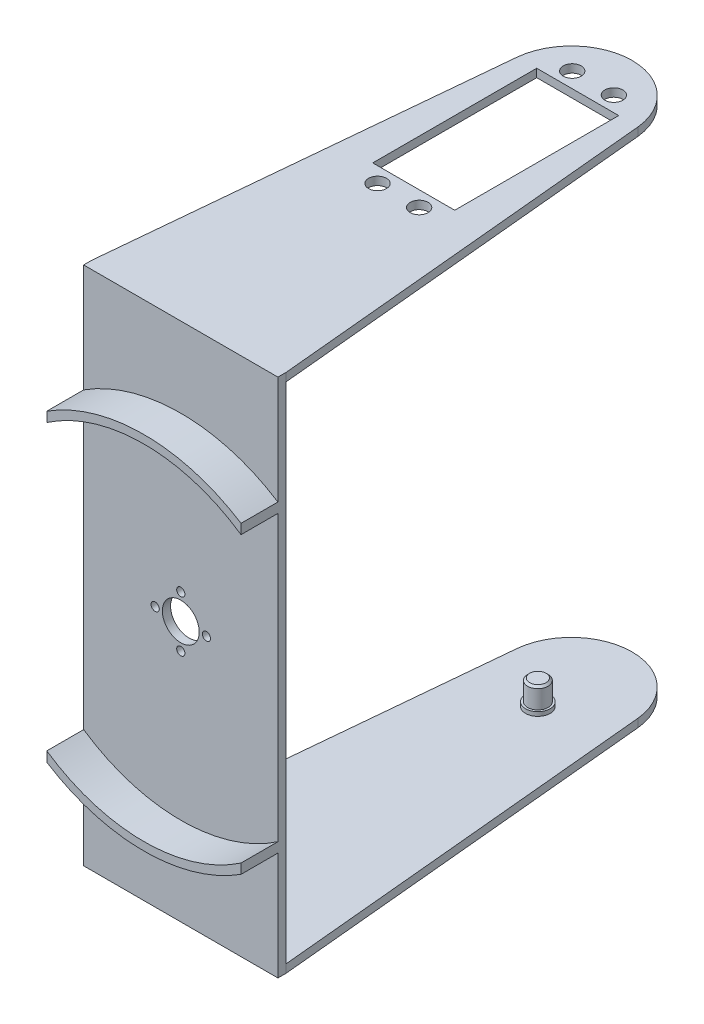
SolidWorks part; units mm, degrees
ref_plane "Front Plane" through (0, 0, 0) normal (0, 0, 1) x (1, 0, 0)
ref_plane "Top Plane" through (0, 0, 0) normal (0, 1, 0) x (1, 0, 0)
ref_plane "Right Plane" through (0, 0, 0) normal (1, 0, 0) x (0, 0, -1)
sketch "Sketch1" plane through (0, 0, 0) normal (0, 1, 0) x (1, 0, 0)
  line L0 (0, 0) -> (10, 0)
  line L1 (10, 0) -> (10, -40)
  line L2 (0, 0) -> (-10, 0)
  line L3 (-10, 0) -> (-10, -40)
  line L4 (-10, -40) -> (10, -40)
  line L5 (0, -46.4243) -> (0, 6.4077) construction
  line L6 (-14.7387, 0) -> (-23.7006, -94.809)
  line L7 (-9.906, -20.0083) -> (9.906, -20.0083) construction
  line L8 (0, -46.4243) -> (0, -94.809) construction
  line L9 (-23.7006, -94.809) -> (0, -94.809) construction
  line L21 (0, 6.4077) -> (0, 0) construction
  line L22 (-9.906, -9.7213) -> (9.906, -9.7213) construction
  line L23 (14.7387, 0) -> (-14.7387, 0) construction
  line L24 (14.7387, 0) -> (23.6804, -94.809)
  line L25 (-23.7006, -94.809) -> (23.6804, -94.809) construction
  line L26 (-23.7006, -94.809) -> (23.6804, -94.809)
  line L27 (-23.7006, -94.809) -> (-23.7006, -96.809)
  line L28 (-23.7006, -96.809) -> (23.6804, -96.809)
  line L29 (23.6804, -96.809) -> (23.6804, -94.809)
  circle A0 centre (-5.08, -43.7573) radius 2.1844
  arc A1 (-6.5248, -45.3956) -> (-3.6352, -45.3956) centre (-5.08, -43.7573) cw
  circle A2 centre (5.08, -43.7573) radius 2.1844
  arc A4 (-14.7387, 0) -> (14.7387, 0) centre (0, -1.5364) cw
  circle A5 centre (5.08, 3.7407) radius 2.1844
  circle A6 centre (-5.08, 3.7407) radius 2.1844
  point P37 (0, 0)
extrude "Boss-Extrude1" add sketch "Sketch1" along normal blind 2 contours A4 L6 L26 L24 L4 L3 L2 L0 L1 A1 region at (-0.0064, 0, 54.2506)
extrude "Boss-Extrude2" add sketch "Sketch1<3>" along normal blind 2 and the other way blind 122.9409 contours L28 L29 L26 L27 region at (-0.0101, 0, 95.809)
sketch "Sketch1<3>" plane through (0, 0, 0) normal (0, 1, 0) x (1, 0, 0) same geometry as "Sketch1"
sketch "Sketch2" plane through (0, -122.9409, 0) normal (0, -1, 0) x (1, 0, 0)
  line L5 (-0.0202, 46.4243) -> (0, 9.7213) construction
  line L6 (14.7185, 0) -> (23.6804, 94.809)
  line L8 (-0.0202, 46.4243) -> (-0.0202, 94.809) construction
  line L9 (23.6804, 94.809) -> (-0.0202, 94.809) construction
  line L10 (0, 9.7213) -> (-0.0202, 0) construction
  line L11 (9.8858, 9.7213) -> (-9.9262, 9.7213) construction
  line L12 (-14.7589, 0) -> (14.7185, 0) construction
  line L13 (-14.7589, 0) -> (-23.7006, 94.809)
  line L14 (23.6804, 94.809) -> (-23.7006, 94.809) construction
  line L15 (23.6804, 94.809) -> (-23.7006, 94.809)
  line L16 (23.6804, 94.809) -> (23.6804, 96.809)
  line L17 (23.6804, 96.809) -> (-23.7006, 96.809)
  line L18 (-23.7006, 96.809) -> (-23.7006, 94.809)
  circle A0 centre (0, 9.7213) radius 3
  circle A1 centre (0, 9.7213) radius 2.5
  arc A3 (14.7185, 0) -> (-14.7589, 0) centre (-0.0202, 1.5364) cw
  point P28 (-0.0202, 0)
  line M2 (23.6804, 96.809) -> (-23.7006, 96.809)
  line M3 (-23.7006, 96.809) -> (-23.7006, 94.809)
  line M4 (-23.7006, 94.809) -> (23.6804, 94.809)
  line M5 (23.6804, 94.809) -> (23.6804, 96.809)
extrude "Boss-Extrude3" add sketch "Sketch2" along normal blind 2 contours A3 L6 L13 A0 M4 | M5 M2 M3 M4 | A0 A1 | A1 region at (-0.0153, -122.9409, 47.0482) region at (-0.0101, -122.9409, 95.809) region at (-2.9151, -122.9409, 9.7213) region at (0, -122.9409, 9.7213)
extrude "Boss-Extrude4" add sketch "Sketch2<3>" against normal blind 1 contours A0 A1 region at (-2.9151, -122.9409, 9.7213)
sketch "Sketch2<3>" plane through (0, -122.9409, 0) normal (0, -1, 0) x (1, 0, 0) same geometry as "Sketch2"
extrude "Boss-Extrude5" add sketch "Sketch2<4>" against normal blind 6 contours A1 region at (0, -122.9409, 9.7213)
sketch "Sketch2<4>" plane through (0, -122.9409, 0) normal (0, -1, 0) x (1, 0, 0) same geometry as "Sketch2"
chamfer "Chamfer1" distance 0.5 angle 45 1 edges at (0, -116.9409, 7.2213)
sketch "Sketch3" plane through (0, 0, 94.809) normal (0, 0, -1) x (-1, 0, 0)
  line L0 (0.0101, 0) -> (0.0101, -122.9409) construction
  line L1 (0.0101, -122.9409) -> (0.0101, -61.4704) construction
  line L2 (4.5101, -61.4704) -> (8.0101, -61.4704) construction
  circle A1 centre (0.0101, -61.4704) radius 4.5
  circle A3 centre (6.2601, -61.4704) radius 1
  circle A4 centre (0.0101, -67.7205) radius 1
  circle A5 centre (-6.2399, -61.4704) radius 1
  circle A6 centre (0.0101, -55.2204) radius 1
  point P16 (0.0101, -61.4704)
  point P19 (0.0101, -61.4704)
extrude "Cut-Extrude1" cut sketch "Sketch3" against normal blind 10
sketch "Sketch4" plane through (0, 0, 96.809) normal (0, 0, 1) x (1, 0, 0)
  line L0 (23.6804, -98.5482) -> (23.6804, -96.1513)
  line L1 (-23.7006, -98.5482) -> (-23.7006, -96.1513)
  line L2 (-23.7006, -24.3927) -> (-23.7006, -26.7896)
  line L3 (23.6804, -24.3927) -> (23.6804, -26.7896)
  circle A0 centre (-0.0101, -61.4704) radius 42
  circle A1 centre (-0.0101, -61.4704) radius 44
  line M6 (23.6804, -124.9409) -> (23.6804, 2)
  line M8 (-23.7006, 2) -> (-23.7006, -124.9409)
extrude "Boss-Extrude6" add sketch "Sketch4" along normal blind 8.998 contours A1 A0 M8 M6 | A1 A0 M6 M8 region at (-0.0101, -104.9876, 96.809) region at (-0.0101, -18.9876, 96.809)
